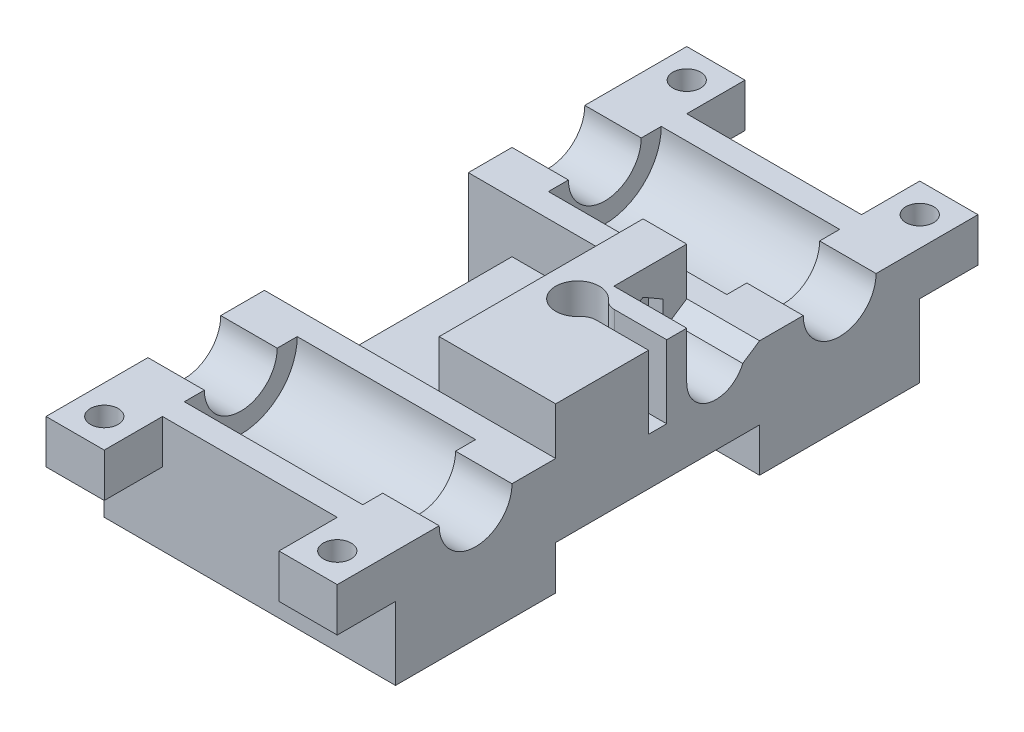
SolidWorks part; units mm, degrees
ref_plane "Front Plane" through (0, 0, 0) normal (0, 0, 1) x (1, 0, 0)
ref_plane "Top Plane" through (0, 0, 0) normal (0, 1, 0) x (1, 0, 0)
ref_plane "Right Plane" through (0, 0, 0) normal (1, 0, 0) x (0, 0, -1)
sketch "Sketch1" plane through (0, 0, 0) normal (0, 1, 0) x (1, 0, 0)
  line L1 (-20, 11) -> (20, 11)
  line L2 (-20, 11) -> (-20, -11)
  line L3 (-20, -11) -> (20, -11)
  line L4 (20, 11) -> (20, -11)
  line L5 (-20, 11) -> (20, -11) construction
  line L6 (-20, -11) -> (20, 11) construction
  point P0 (0, 0)
  dimension "D1" = 40
  dimension "D2" = 22
extrude "Boss-Extrude1" add sketch "Sketch1" along normal blind 11
sketch "Sketch2" plane through (0, 0, 0) normal (0, 1, 0) x (1, 0, 0)
  line L4 (20, -11) -> (20, 11)
  line L5 (-20, -11) -> (20, -11)
  line L6 (-20, 11) -> (-20, -11)
  line L7 (20, 11) -> (-20, 11)
  line L8 (20, -11) -> (20, 11)
  line L9 (-20, -11) -> (20, -11)
  line L10 (-20, 11) -> (-20, -11)
  line L11 (20, 11) -> (-20, 11)
  circle A0 centre (0, 0) radius 7.8438
  dimension "D1" = 0
extrude "Boss-Extrude2" add sketch "Sketch2" against normal blind 5
sketch "Sketch3" plane through (0, 11, 0) normal (0, 1, 0) x (1, 0, 0)
  line L1 (12.25, -7.75) -> (-12.25, -7.75)
  line L2 (12.25, -7.75) -> (12.25, 7.75)
  line L3 (12.25, 7.75) -> (-12.25, 7.75)
  line L4 (-12.25, -7.75) -> (-12.25, 7.75)
  line L5 (12.25, -7.75) -> (-12.25, 7.75) construction
  line L6 (12.25, 7.75) -> (-12.25, -7.75) construction
  point P0 (0, 0)
  dimension "D1" = 15.5
  dimension "D2" = 24.5
extrude "Cut-Extrude1" cut sketch "Sketch3" against normal blind 7.75
fillet "Fillet1" radius 7.75 2 edges at (0, 3.25, 7.75) (0, 3.25, -7.75)
sketch "Sketch4" plane through (-12.25, 0, 0) normal (1, 0, 0) x (0, 0, -1)
  line L0 (7.75, 11) -> (-7.75, 11) construction
  circle A0 centre (0, 11) radius 5
  dimension "D1" = 10
extrude "Cut-Extrude2" cut sketch "Sketch4" against normal through all both and the other way through all
sketch "Sketch5" plane through (0, 11, 0) normal (0, 1, 0) x (1, 0, 0)
  line L1 (20, -11) -> (12, -11)
  line L2 (20, -11) -> (20, -19)
  line L3 (20, -19) -> (12, -19)
  line L4 (12, -11) -> (12, -19)
  circle A0 centre (16, -15) radius 1.9058
  dimension "D1" = 8
  dimension "D2" = 8
  dimension "D3" = 4
  dimension "D4" = 4
extrude "Boss-Extrude3" add sketch "Sketch5" against normal blind 6
sketch "Sketch6" plane through (0, 5, 0) normal (0, -1, 0) x (1, 0, 0)
  line L4 (20, 11) -> (20, 19)
  line L5 (20, 19) -> (12, 19)
  line L6 (12, 19) -> (12, 11)
  line L7 (12, 11) -> (20, 11)
  line L8 (20, 11) -> (20, 19)
  line L9 (20, 19) -> (12, 19)
  line L10 (12, 19) -> (12, 11)
  line L11 (12, 11) -> (20, 11)
  circle A0 centre (16, 15) radius 1.9058 construction
  circle A1 centre (16, 15) radius 1.9058
  circle A2 centre (16, 15) radius 3
  circle M6 centre (16, 15) radius 1.9058
  dimension "D2" = 6
  dimension "D1" = 0
extrude "Cut-Extrude3" cut sketch "Sketch6" against normal blind 3 contours A2 M6
mirror "Mirror8" about plane through (0, 0, 0) normal (1, 0, 0) of "Cut-Extrude3", "Boss-Extrude3"
mirror "Mirror9" [suppressed] about plane through (0, 0, 0) normal (0, 0, 1)
chamfer "Chamfer2" [suppressed] distance 4 angle 45
ref_plane "Plane1" through (0, 0, -25) normal (0, 0, 1) x (1, 0, 0)
sketch "Sketch7" plane through (0, 0, -11) normal (0, 0, -1) x (-1, 0, 0)
  line L0 (-20, 11) -> (-20, -5) construction
  line L1 (-20, 1) -> (-4, 1)
  line L2 (-20, 1) -> (-20, 17.5)
  line L3 (-20, 17.5) -> (-4, 17.5)
  line L4 (-4, 1) -> (-4, 17.5)
  line L5 (-20, 11) -> (20, 11) construction
  dimension "D1" = 16
  dimension "D2" = 16.5
  dimension "D3" = 6.5
extrude "Boss-Extrude5" add sketch "Sketch7" along normal blind 28
mirror "Mirror14" about plane through (0, 0, -25) normal (0, 0, 1) of "Mirror8", "Cut-Extrude3", "Boss-Extrude3", "Cut-Extrude2", "Fillet1", "Cut-Extrude1", "Boss-Extrude2", "Boss-Extrude1"
sketch "Sketch9" plane through (4, 0, 0) normal (-1, 0, 0) x (0, 0, 1)
  line L0 (-39, 1) -> (-39, 11) construction
  line L1 (-11, 1) -> (-39, 1)
  line L2 (-11, 1) -> (-11, 4)
  line L3 (-11, 4) -> (-39, 4)
  line L4 (-39, 1) -> (-39, 4)
  dimension "D1" = 3
extrude "Boss-Extrude6" add sketch "Sketch9" along normal blind 18
sketch "Sketch10" plane through (0, 17.5, 0) normal (0, 1, 0) x (1, 0, 0)
  line L0 (-8.8, 25) -> (8.8, 25) construction
  line L1 (20, 39) -> (20, 11) construction
  line L3 (9, 23.75) -> (20, 23.75)
  line L4 (9, 23.75) -> (9, 26.25)
  line L5 (9, 26.25) -> (20, 26.25)
  line L6 (20, 23.75) -> (20, 26.25)
  circle A0 centre (9, 25) radius 3
  line M4 (20, 11) -> (20, 39)
  dimension "D3" = 6
  dimension "D1" = 0
  dimension "D2" = 11
  dimension "D4" = 2.5
  dimension "D5" = 1.25
extrude "Cut-Extrude4" cut sketch "Sketch10" against normal blind 10 contours L3 A0 L5 L4 | L5 A0 L3 L4 | A0 L3 L5 M4
sketch "Sketch11" plane through (0, 7.5, 0) normal (0, 1, 0) x (1, 0, 0)
  arc A0 (11.7272, 26.25) -> (11.7272, 23.75) centre (9, 25) ccw construction
  arc A1 (11.7272, 26.25) -> (11.7272, 23.75) centre (9, 25) ccw
  circle A2 centre (9, 25) radius 1.75
  dimension "D1" = 3.5
extrude "Cut-Extrude5" cut sketch "Sketch11" against normal through all both and the other way through all contours A2
sketch "Sketch12" plane through (4, 0, 0) normal (-1, 0, 0) x (0, 0, 1)
  line L1 (-39, 4) -> (-39, 11) construction
  circle A0 centre (-33, 11) radius 1.75
  dimension "D3" = 3.5
  dimension "D1" = 0
  dimension "D2" = 6
extrude "Cut-Extrude6" cut sketch "Sketch12" against normal through all both and the other way through all
sketch "Sketch15" plane through (20, 0, 0) normal (1, 0, 0) x (0, 0, -1)
  line L1 (33, 14.1754) -> (30.25, 12.5877)
  line L2 (30.25, 12.5877) -> (30.25, 9.4123)
  line L3 (30.25, 9.4123) -> (33, 7.8246)
  line L4 (33, 7.8246) -> (35.75, 9.4123)
  line L5 (35.75, 9.4123) -> (35.75, 12.5877)
  line L6 (35.75, 12.5877) -> (33, 14.1754)
  circle A0 centre (33, 11) radius 1.75 construction
  circle A1 centre (33, 11) radius 1.75
  circle A2 centre (33, 11) radius 2.75 construction
  dimension "D1" = 5.5
extrude "Cut-Extrude9" cut sketch "Sketch15" against normal blind 12 contours L1 L2 L3 L4 L5 L6
sketch "Sketch16" plane through (20, 0, 0) normal (1, 0, 0) x (0, 0, -1)
  line L1 (29, 11) -> (39, 11)
  line L2 (29, 11) -> (29, 17.5)
  line L3 (29, 17.5) -> (39, 17.5)
  line L4 (39, 11) -> (39, 17.5)
  circle A0 centre (33, 11) radius 1.75 construction
  circle A1 centre (33, 11) radius 1.75
  circle A2 centre (33, 11) radius 4
  dimension "D1" = 8
extrude "Cut-Extrude11" cut sketch "Sketch16" against normal blind 10
chamfer "Chamfer3" distance 2.5 angle 45 1 edges at (15, 11, -37)
fillet "Fillet2" radius 2 2 edges at (11.7272, 12.5, -23.75) (11.7272, 12.5, -26.25)
sketch "Sketch17" plane through (0, 1, 0) normal (0, -1, 0) x (1, 0, 0)
  line L1 (12.1754, -25) -> (10.5877, -22.25)
  line L2 (10.5877, -22.25) -> (7.4123, -22.25)
  line L3 (7.4123, -22.25) -> (5.8246, -25)
  line L4 (5.8246, -25) -> (7.4123, -27.75)
  line L5 (7.4123, -27.75) -> (10.5877, -27.75)
  line L6 (10.5877, -27.75) -> (12.1754, -25)
  circle A0 centre (9, -25) radius 1.75 construction
  circle A1 centre (9, -25) radius 1.75
  circle A2 centre (9, -25) radius 2.75 construction
  dimension "D1" = 5.5
extrude "Cut-Extrude12" cut sketch "Sketch17" against normal blind 3
